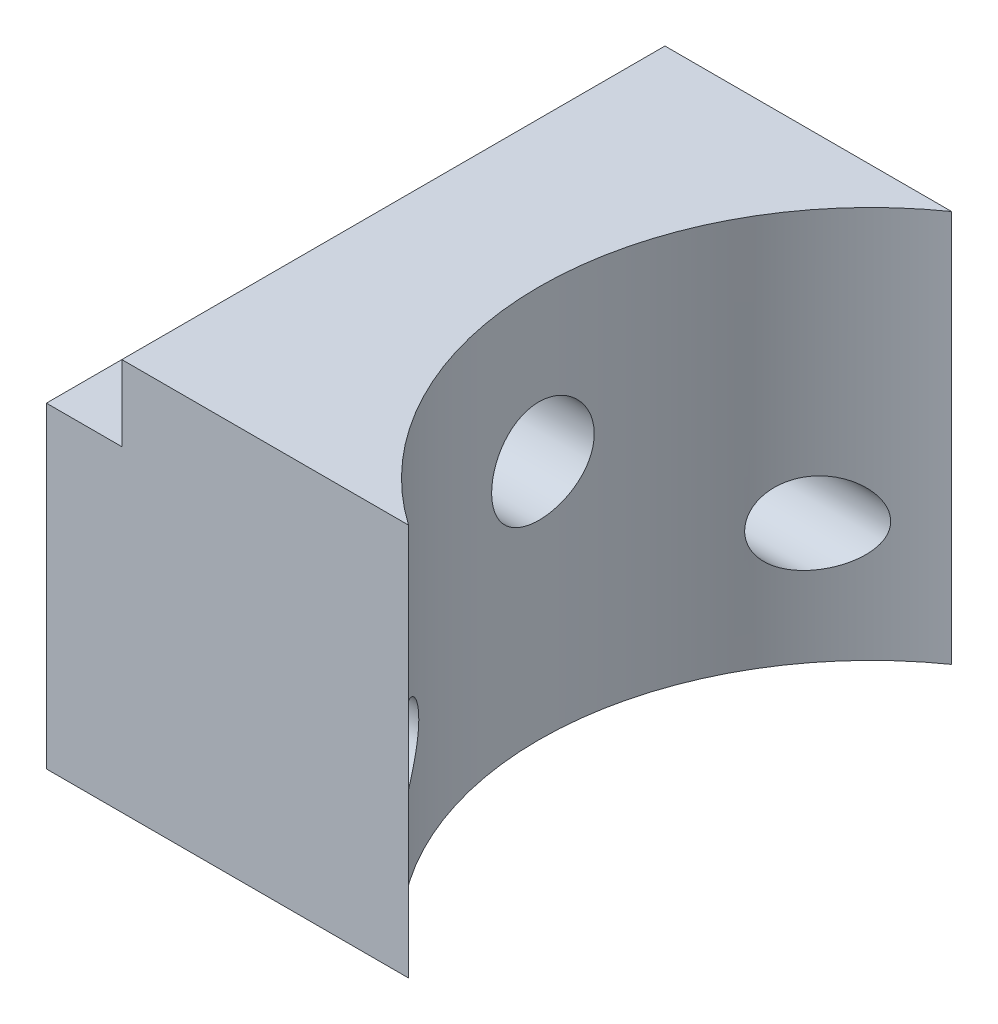
SolidWorks part; units mm, degrees
ref_plane "Front Plane" through (0, 0, 0) normal (0, 0, 1) x (1, 0, 0)
ref_plane "Top Plane" through (0, 0, 0) normal (0, 1, 0) x (1, 0, 0)
ref_plane "Right Plane" through (0, 0, 0) normal (1, 0, 0) x (0, 0, -1)
sketch "Sketch1" plane through (0, 0, 0) normal (0, 1, 0) x (1, 0, 0)
  line L0 (0, 9) -> (0, -9)
  line L1 (0, -9) -> (12, -9)
  line L2 (12, 9) -> (0, 9)
  arc A1 (12, 9) -> (12, -9) centre (18.3246, 0) ccw
  point P7 (0, 0)
  dimension "D1" = 22
  dimension "D2" = 18
  dimension "D3" = 12
extrude "Boss-Extrude1" add sketch "Sketch1" along normal blind 13
sketch "Sketch10" plane through (0, 0, 0) normal (-1, 0, 0) x (0, 0, 1)
  point P0 (0, 8)
  dimension "D1" = 8
hole_wizard "CSK for M3 SFHCS1" positions "Sketch10" profile "Sketch11" countersink size "M3" standard "ANSI Metric" end condition up to next
sketch "Sketch11" plane through (0, 8, 0) normal (0, 1, 0) x (0, 0, 1)
  line L0 (0, 0) -> (0, 7.3246)
  line L1 (0, 7.3246) -> (1.7, 7.3246)
  line L2 (1.7, 7.3246) -> (1.7, 4.66)
  line L3 (1.7, 4.66) -> (3.36, 3)
  line L4 (3.36, 3) -> (3.36, 0)
  line L6 (3.36, 0) -> (0, 0)
  line L7 (-1.7, 4.66) -> (-3.36, 3) construction
  line L11 (0, -6.35) -> (0, 107.95) construction
  dimension "Thru Hole Dia." = 3.4
  dimension "Thru Hole Depth" = 7.3246
  dimension "C'Sink Dia." = 6.72
  dimension "C'Sink Angle" = 90
  dimension "Head Clearance" = 3
sketch "Sketch12" plane through (0, 0, 0) normal (-1, 0, 0) x (0, 0, 1)
  line L0 (-6.75, 4) -> (6.75, 4) construction
  line L1 (-9, 0) -> (9, 0) construction
  point P0 (-6.75, 4)
  point P1 (6.75, 4)
  point P3 (0, 4)
  dimension "D1" = 4
  dimension "D2" = 13.5
hole_wizard "Ø2.7 (2.7) Diameter Hole1" positions "Sketch12" profile "Sketch14" hole size "Ø2.7" standard "ANSI Metric" end condition up to next
sketch "Sketch14" plane through (0, 4, -6.75) normal (0, 1, 0) x (0, 0, 1)
  line L0 (0, 0) -> (0, 9.6391)
  line L1 (0, 9.6391) -> (1.35, 9.6391)
  line L2 (1.35, 9.6391) -> (1.35, 0)
  line L5 (1.35, 0) -> (0, 0)
  line L11 (0, -6.35) -> (0, 107.95) construction
  dimension "Thru Hole Dia." = 2.7
  dimension "Thru Hole Depth" = 9.6391
sketch "Sketch15" plane through (0, 0, 0) normal (-1, 0, 0) x (0, 0, 1)
  line L0 (9, 13) -> (9, 0) construction
  line L1 (-9, 13) -> (9, 13)
  line L2 (-9, 13) -> (-9, 10.5)
  line L3 (-9, 10.5) -> (9, 10.5)
  line L4 (9, 13) -> (9, 10.5)
  dimension "D1" = 2.5
extrude "Cut-Extrude1" cut sketch "Sketch15" against normal blind 2.5
